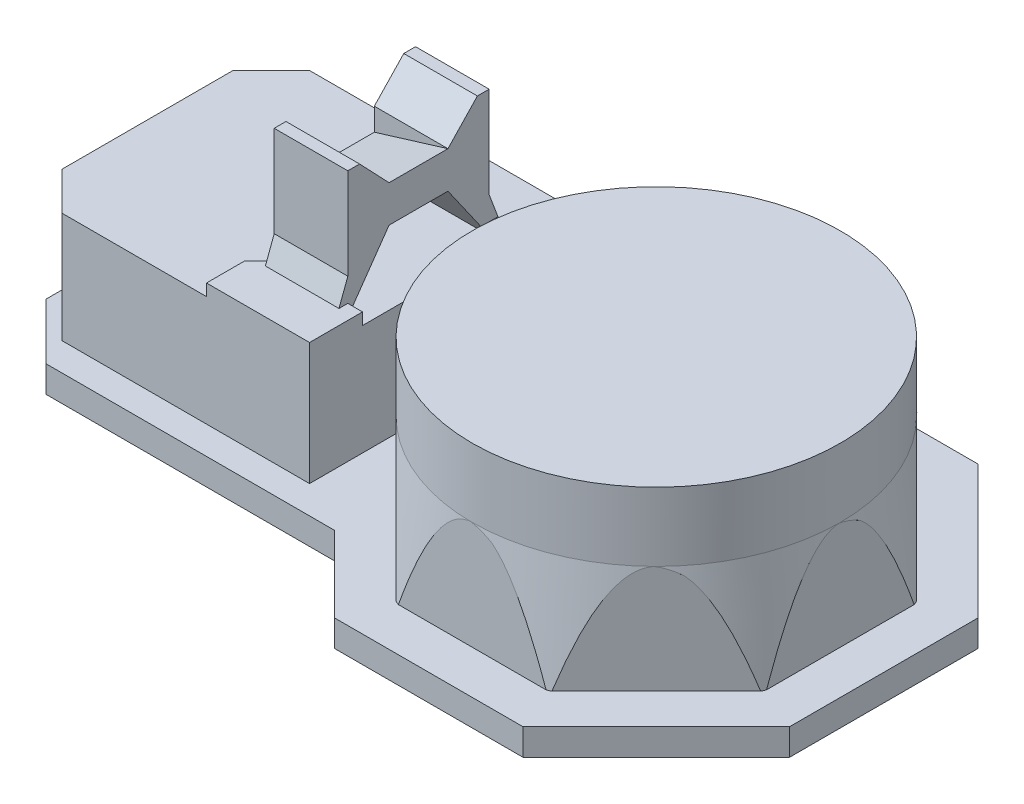
SolidWorks part; units mm, degrees
ref_plane "前视基准面" through (0, 0, 0) normal (0, 0, 1) x (1, 0, 0)
ref_plane "上视基准面" through (0, 0, 0) normal (0, 1, 0) x (1, 0, 0)
ref_plane "右视基准面" through (0, 0, 0) normal (1, 0, 0) x (0, 0, -1)
sketch "草图1" plane through (0, 0, 0) normal (0, 1, 0) x (1, 0, 0)
  line L0 (81.4697, 0) -> (-246.302, 0) construction
  line L1 (81.4697, 32) -> (36.2149, 77.2548)
  line L2 (36.2149, 77.2548) -> (-27.7851, 77.2548)
  line L3 (-27.7851, 77.2548) -> (-53.54, 51.5)
  line L5 (-53.54, -51.5) -> (-27.7851, -77.2548)
  line L6 (-27.7851, -77.2548) -> (36.2149, -77.2548)
  line L7 (36.2149, -77.2548) -> (81.4697, -32)
  line L8 (81.4697, -32) -> (81.4697, 32)
  line L10 (-170.54, -51.5) -> (-53.54, -51.5)
  line L11 (-170.54, -51.5) -> (-170.54, 51.5)
  line L12 (-170.54, 51.5) -> (-53.54, 51.5)
  line L16 (-73.04, 0) -> (-73.04, -32) [skipped]
  point P13 (-116.2548, 0)
  dimension "D1" = 64
  dimension "D2" = 103
  dimension "D3" = 117
extrude "凸台-拉伸1" add sketch "草图1" along normal blind 9
sketch "草图2" plane through (0, 9, 0) normal (0, 1, 0) x (1, 0, 0)
  line L0 (-170.54, 0) -> (81.4697, 0) construction
  line L1 (-170.54, 51.5) -> (-170.54, -51.5) construction
  line L2 (81.4697, -32) -> (81.4697, 32) construction
  line L3 (-170.54, 32.5) -> (-170.54, -32.5)
  line L4 (-170.54, 0) -> (-48.7057, 0) construction
  line L5 (-170.54, 32.5) -> (-151.54, 51.5)
  line L6 (-53.54, 51.5) -> (-170.54, 51.5) construction
  line L7 (-170.54, -32.5) -> (-151.54, -51.5)
  line L8 (-170.54, -51.5) -> (-53.54, -51.5) construction
  line L9 (-151.54, -51.5) -> (-170.54, -51.5)
  line L10 (-170.54, -51.5) -> (-170.54, -32.5)
  line L11 (-151.54, 51.5) -> (-170.54, 51.5)
  line L12 (-170.54, 51.5) -> (-170.54, 32.5)
  line M10 (-53.54, 51.5) -> (-170.54, 51.5)
  line M11 (-170.54, 51.5) -> (-170.54, -51.5)
  line M12 (-170.54, -51.5) -> (-53.54, -51.5)
  dimension "D1" = 65
  dimension "D2" = 45
  dimension "D3" = 45
extrude "切除-拉伸2" cut sketch "草图2" along direction (0, 1, 0) on the side against the normal up to surface (9 mm away) contours L7 M11 M12 | L5 M11 M10 region at (-164.2066, 9, 45.1667) region at (-164.2066, 9, -45.1667) up to face at (-26.8361, 0, 0)
sketch "草图4" plane through (0, 9, 0) normal (0, 1, 0) x (1, 0, 0)
  line L0 (36.2149, 77.2548) -> (-27.7851, 77.2548) construction
  line L1 (81.4697, 32) -> (36.2149, 77.2548) construction
  line L3 (-53.54, -51.5) -> (-27.7851, -77.2548) construction
  line L4 (-27.7851, -77.2548) -> (36.2149, -77.2548) construction
  circle A0 centre (4.2149, 0) radius 77.2548 construction
  circle A1 centre (4.2149, 0) radius 63.5
  dimension "D1" = 127
extrude "凸台-拉伸2" add sketch "草图4" along normal blind 60
sketch "草图5" plane through (0, 9, 0) normal (0, 1, 0) x (1, 0, 0)
  line L1 (-155.54, -42) -> (-61.54, -42)
  line L2 (-168.54, -29) -> (-168.54, 29)
  line L3 (-155.54, 42) -> (-61.54, 42)
  line L4 (-61.54, -42) -> (-61.54, 42)
  line L5 (-157.2221, -40.3179) -> (-61.54, 42) construction
  line L6 (-157.2221, 40.3179) -> (-61.54, -42) construction
  line L7 (-170.54, 0) -> (-95.364, 0) construction
  line L8 (-170.54, 32.5) -> (-170.54, -32.5) construction
  line L9 (-155.54, 42) -> (-168.54, 29)
  line L10 (-170.54, 32.5) -> (-151.54, 51.5) construction
  line L11 (-168.54, -29) -> (-155.54, -42)
  line L12 (-170.54, -32.5) -> (-151.54, -51.5) construction
  line L13 (-61.54, 0) -> (-126.9039, 0) construction
  point P0 (-110.3587, 0)
  dimension "D1" = 84
  dimension "D2" = 58
  dimension "D3" = 94
  dimension "D4" = 2
extrude "凸台-拉伸3" add sketch "草图5" along normal blind 37.5
sketch "草图6" plane through (0, 9, 0) normal (0, 1, 0) x (1, 0, 0)
  line L9 (61.8255, 26.7069) -> (26.0671, 59.6215)
  line L10 (26.0671, 59.6215) -> (-22.492, 57.6107)
  line L11 (-22.492, 57.6107) -> (-55.4067, 21.8523)
  line L12 (-55.4067, 21.8523) -> (-53.3958, -26.7069)
  line L13 (-53.3958, -26.7069) -> (-17.6374, -59.6215)
  line L14 (-17.6374, -59.6215) -> (30.9218, -57.6107)
  line L15 (30.9218, -57.6107) -> (63.8364, -21.8523)
  line L16 (63.8364, -21.8523) -> (61.8255, 26.7069)
  circle A0 centre (4.2149, 0) radius 63.5 construction
  circle A2 centre (4.2149, 0) radius 63.5 construction
  circle A3 centre (4.2149, 0) radius 58.6664
sketch "草图7" plane through (0, 46.5, 0) normal (0, 1, 0) x (1, 0, 0)
  line L0 (-61.54, -42) -> (-61.54, 42) construction
  line L1 (-106.54, 42) -> (-61.54, 42)
  line L2 (-106.54, 42) -> (-106.54, 29)
  line L4 (-61.54, 42) -> (-61.54, 29)
  line L5 (-61.54, 42) -> (-155.54, 42) construction
  line L6 (-106.54, -29) -> (-101.5572, -24)
  line L7 (-61.54, -42) -> (-106.54, -42)
  line L8 (-61.54, -42) -> (-61.54, -29)
  line L10 (-106.54, -42) -> (-106.54, -29)
  line L11 (-61.54, -29) -> (-66.5228, -24)
  line L12 (-101.5572, -24) -> (-66.5228, -24)
  line L13 (-66.54, 24) -> (-101.54, 24)
  line L14 (-106.54, 29) -> (-101.54, 24)
  line L15 (-61.54, 29) -> (-66.54, 24)
  dimension "D1" = 45
  dimension "D2" = 13
  dimension "D3" = 18
  dimension "D4" = 18
extrude "凸台-拉伸4" add sketch "草图7" along normal blind 4
ref_plane "基准面4" through (-101.54, 0, 0) normal (-1, 0, 0) x (0, 0, 1)
sketch "草图8" plane through (-101.54, 0, 0) normal (-1, 0, 0) x (0, 0, 1)
  line L0 (-24, 46.5) -> (-10, 66.5)
  line L1 (-10, 66.5) -> (10, 66.5)
  line L2 (10, 66.5) -> (24, 46.5)
  line L5 (-29, 46.5) -> (29, 46.5) construction
  line L6 (0, 66.5) -> (0, 54.3492) construction
  line L7 (0, 46.5) -> (0, 57.066) construction
  line L8 (-24, 46.5) -> (-24, 89.5)
  line L9 (-24, 89.5) -> (-20, 89.5)
  line L11 (-10, 75) -> (10, 75)
  line L13 (20, 89.5) -> (24, 89.5)
  line L14 (24, 89.5) -> (24, 46.5)
  line L15 (-10, 75) -> (-10, 79)
  line L16 (-10, 79) -> (-20, 89.5)
  line L17 (10, 75) -> (10, 79)
  line L18 (10, 79) -> (20, 89.5)
  dimension "D1" = 20
  dimension "D2" = 8.5
  dimension "D3" = 20
  dimension "D4" = 43
  dimension "D5" = 4
  dimension "D6" = 4
  dimension "D7" = 4
  dimension "D8" = 4
ref_plane "基准面5" through (-23.4269, 87.4303, 0) normal (-0.2588, 0.9659, 0) x (0, 0, 1)
sketch "草图9" plane through (-23.4269, 87.4303, 0) normal (-0.2588, 0.9659, 0) x (0, 0, 1)
sketch "草图10" plane through (-23.4269, 87.4303, 0) normal (-0.2588, 0.9659, 0) x (0, 0, 1)
  line L0 (0, -78.6687) -> (0, -53.6687)
  line L1 (-10, -78.6687) -> (10, -78.6687) construction
  dimension "D1" = 25
ref_plane "基准面6" through (-76.54, 0, 0) normal (-1, 0, 0) x (0, 0, 1)
extrude "凸台-拉伸5" add sketch "草图8" against normal blind 25
sketch "草图12" plane through (-101.54, 0, 0) normal (-1, 0, 0) x (0, 0, 1)
  line L0 (-24, 58.5) -> (-27, 50.5)
  line L1 (-24, 89.5) -> (-24, 50.5) construction
  line L2 (-27, 50.5) -> (-24, 50.5)
  line L3 (-24, 50.5) -> (-24, 46.5) construction
  line L4 (-24, 50.5) -> (-24, 58.5)
  dimension "D1" = 3
  dimension "D2" = 8
extrude "凸台-拉伸6" add sketch "草图12" against normal up to surface (25 mm away) up to face at (-76.54, 70.9286, 0)
sketch "草图14" plane through (0, 50.5, 0) normal (0, 1, 0) x (1, 0, 0)
  line L0 (-104.54, 27) -> (-101.54, 27)
  line L1 (-101.54, 16.3055) -> (-101.54, -16.3055) construction
  line L2 (-101.54, 27) -> (-101.54, 24)
  line L3 (-106.54, 29) -> (-101.54, 24) construction
  line L4 (-101.54, 24) -> (-104.54, 27)
  line L5 (-76.54, 27) -> (-101.54, 27) construction
sketch "草图15" plane through (-101.54, 0, 0) normal (-1, 0, 0) x (0, 0, 1)
  line L0 (24, 50.5) -> (27, 50.5)
  line L1 (24, 50.5) -> (29, 50.5) construction
  line L2 (27, 50.5) -> (24, 58.5)
  line L3 (24, 50.5) -> (24, 89.5) construction
  line L4 (24, 58.5) -> (24, 50.5)
  dimension "D1" = 3
  dimension "D2" = 8
extrude "凸台-拉伸7" add sketch "草图15" against normal up to surface (25 mm away) up to face at (-76.54, 68.875, -3.1875)
ref_plane "Plane1" through (0, 0, 63.5) normal (0, 0, 1) x (1, 0, 0)
sketch "Sketch4" plane through (0, 69, 0) normal (0, 1, 0) x (1, 0, 0)
  circle A0 centre (4.2149, 0) radius 62.5
  circle A1 centre (4.2149, 0) radius 63.5 construction
  circle M2 centre (4.2149, 0) radius 63.5
  dimension "D1" = 125
extrude "Cut-Extrude2" cut sketch "Sketch4" against normal up to surface (60 mm away) contours A0 M2 region at (-59.1055, 69, 0) up to face at (4.2149, 9, 63.5)
ref_plane "Plane2" through (0, 0, 0) normal (0, 0, 1) x (1, 0, 0)
sketch "Sketch9" plane through (0, 0, 0) normal (0, 0, 1) x (1, 0, 0)
  line L0 (66.7149, 45.6989) -> (71.5572, 9)
  line L1 (66.7149, 9) -> (66.7149, 69) construction
  line L2 (36.2149, 9) -> (81.4697, 9) construction
  line L4 (66.7149, 9) -> (66.7149, 45.6989)
  line L5 (4.2149, 69) -> (4.2149, 98.0548) construction
  line L6 (66.7149, 69) -> (-58.2851, 69) construction
  line L7 (66.7149, 9) -> (71.5572, 9)
revolve "Revolve2" add sketch "Sketch9" angle 360 about L5
ref_plane "Plane4" through (0, 0, 62.5) normal (0, 0, 1) x (1, 0, 0)
sketch "Sketch12" plane through (0, 0, 62.5) normal (0, 0, 1) x (1, 0, 0)
  line L0 (66.7149, 45.6989) -> (-58.2851, 45.6989) construction
  line L2 (36.2149, 9) -> (-27.7851, 9)
  spline S0 degree 2 poles (-27.7851, 9) (-0.6048, 82.634) (36.2149, 9) knots 0 0 0 1 1 1
extrude "Cut-Extrude4" cut sketch "Sketch12" along normal blind 6.8
pattern_circular "CirPattern1" count 8 over 360 about axis through (4.2149, 69, 0) along (0, 1, 0) of "Cut-Extrude4"
sketch "Sketch15" plane through (-61.54, 0, 0) normal (1, 0, 0) x (0, 0, -1)
  line L1 (-33.7212, 39.1331) -> (39.7757, 39.1331)
  line L2 (-33.7212, 39.1331) -> (-33.7212, 6.083)
  line L3 (-33.7212, 6.083) -> (39.7757, 6.083)
  line L4 (39.7757, 39.1331) -> (39.7757, 6.083)
extrude "Boss-Extrude4" add sketch "Sketch15" against normal blind 16
sketch "Sketch16" plane through (0, 75, 0) normal (0, 1, 0) x (1, 0, 0)
  line L0 (-101.54, 10) -> (-76.54, 10)
  line L1 (-76.54, -10) -> (-76.54, 10) construction
  line L2 (-76.54, 10) -> (-101.54, 10) construction
  line L3 (-76.54, 10) -> (-76.54, -10)
  line L4 (-76.54, -10) -> (-101.54, -10)
  line L5 (-101.54, -10) -> (-101.54, 10) construction
  line L6 (-76.54, -10) -> (-101.54, -10) construction
  line L7 (-101.54, -10) -> (-101.54, 10)
extrude "Boss-Extrude5" add sketch "Sketch16" along normal blind 10
sketch "Sketch17" plane through (0, 0, 10) normal (0, 0, 1) x (1, 0, 0)
  line L0 (-76.54, 79) -> (-101.54, 71.3481)
  line L2 (-101.54, 58.5) -> (-101.54, 89.5) construction
  line L5 (-101.54, 71.3481) -> (-101.54, 89.5)
  line L6 (-101.54, 89.5) -> (-76.54, 89.5)
  line L7 (-76.54, 89.5) -> (-76.54, 79)
extrude "Cut-Extrude5" cut sketch "Sketch17" against normal up to surface (20 mm away) up to face at (-89.04, 82, -10)
sketch "Sketch19" plane through (0, 50.5, 0) normal (0, 1, 0) x (1, 0, 0)
  line L0 (-155.54, -42) -> (-61.54, -42) construction
  line L1 (-61.54, 42) -> (-71.54, 42)
  line L2 (-61.54, 42) -> (-61.54, -42)
  line L3 (-61.54, -42) -> (-71.54, -42)
  line L4 (-71.54, 42) -> (-71.54, -42)
  dimension "D1" = 10
extrude "Cut-Extrude6" cut sketch "Sketch19" against normal up to surface (41.5 mm away) contours L2 L1 L4 L3 up to face at (-128.54, 9, 0)
ref_axis "Axis1" through (-9.8161, 95.75, -5.2169) along (0.9373, 0, 0.3485)
ref_plane "Plane5" through (3.7029, 0, 1.3768) normal (-0.9373, 0, -0.3485) x (-0.3485, 0, 0.9373)
ref_point "Point1"
